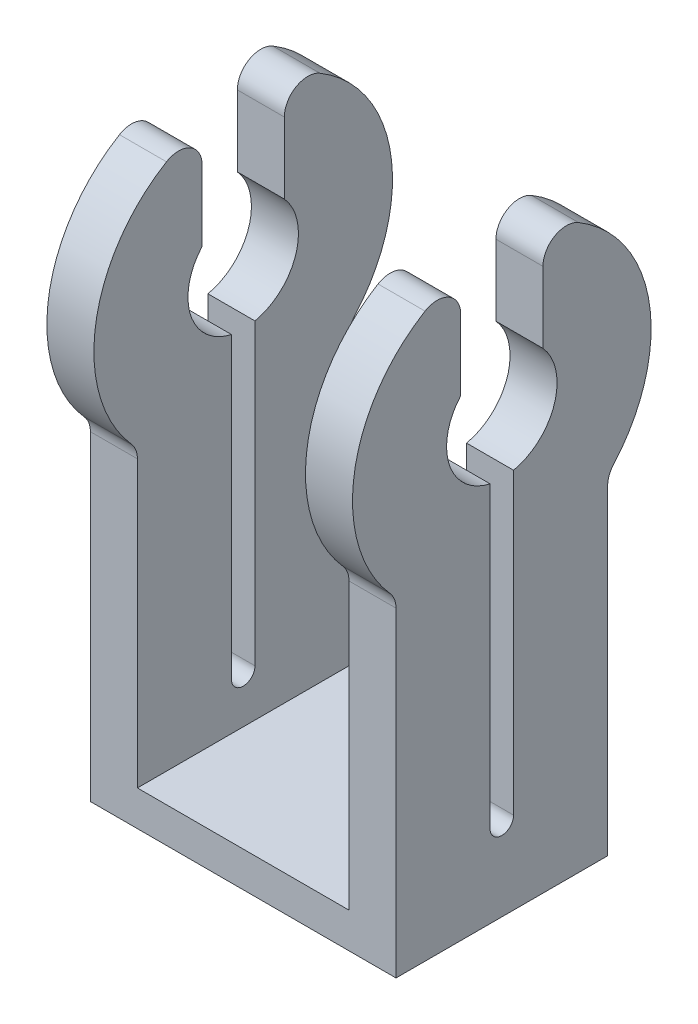
SolidWorks part; units mm, degrees
ref_plane "Front Plane" through (0, 0, 0) normal (0, 0, 1) x (1, 0, 0)
ref_plane "Top Plane" through (0, 0, 0) normal (0, 1, 0) x (1, 0, 0)
ref_plane "Right Plane" through (0, 0, 0) normal (1, 0, 0) x (0, 0, -1)
sketch "Sketch1" plane through (0, 0, 0) normal (0, 1, 0) x (1, 0, 0)
  line L1 (6.5, -4.5) -> (-6.5, -4.5)
  line L2 (6.5, -4.5) -> (6.5, 4.5)
  line L3 (6.5, 4.5) -> (-6.5, 4.5)
  line L4 (-6.5, -4.5) -> (-6.5, 4.5)
  line L5 (6.5, -4.5) -> (-6.5, 4.5) construction
  line L6 (6.5, 4.5) -> (-6.5, -4.5) construction
  point P0 (0, 0)
  dimension "D1" = 13
  dimension "D2" = 9
extrude "Boss-Extrude1" add sketch "Sketch1" along normal blind 1.5
sketch "Sketch2" plane through (-6.5, 0, 0) normal (-1, 0, 0) x (0, 0, 1)
  line L0 (0, 1.5) -> (0, 18.5) construction
  line L1 (-4.5, 1.5) -> (4.5, 1.5) construction
  line L2 (-4.5, 1.5) -> (4.5, 1.5)
  line L3 (-4.5, 1.5) -> (-4.5, 14.0198)
  line L4 (0, 18.5) -> (0, 3.5) construction
  line L5 (4.5, 1.5) -> (4.5, 14.0198)
  line L6 (0.5, 16.2038) -> (0.5, 3.5)
  line L7 (-0.5, 16.2038) -> (-0.5, 3.5)
  line L8 (-1.75, 20.0684) -> (-1.75, 24.6041)
  line L9 (1.75, 24.6041) -> (1.75, 20.0684)
  line L10 (0, 18.5) -> (0, 24.85) construction
  line L11 (1.75, 24.85) -> (-1.75, 24.85) construction
  arc A0 (-1.75, 20.0684) -> (-0.5, 16.2038) centre (0, 18.5) ccw
  arc A3 (-0.5, 3.5) -> (0.5, 3.5) centre (0, 3.5) ccw
  arc A4 (4.5, 14.0198) -> (1.75, 24.6041) centre (0, 18.5) ccw
  arc A5 (-1.75, 24.6041) -> (-4.5, 14.0198) centre (0, 18.5) ccw
  arc A6 (0.5, 16.2038) -> (1.75, 20.0684) centre (0, 18.5) ccw
  point P5 (0, 23.6163)
  point P11 (0, 11)
  point P15 (0, 0)
  point P25 (0, 0)
  point P28 (0, 24.85)
  point P29 (0, 0)
  dimension "D2" = 4.7
  dimension "D3" = 4
  dimension "D1" = 17
  dimension "D4" = 1
  dimension "D5" = 15
  dimension "D6" = 3.5
extrude "Boss-Extrude2" add sketch "Sketch2" against normal blind 2
fillet "Fillet1" radius 1 4 edges at (-5.5, 14.0198, 4.5) (-5.5, 14.0198, -4.5) (-5.5, 24.6041, 1.75) (-5.5, 24.6041, -1.75)
mirror "Mirror1" about plane through (0, 0, 0) normal (1, 0, 0) of "Fillet1", "Boss-Extrude2"
